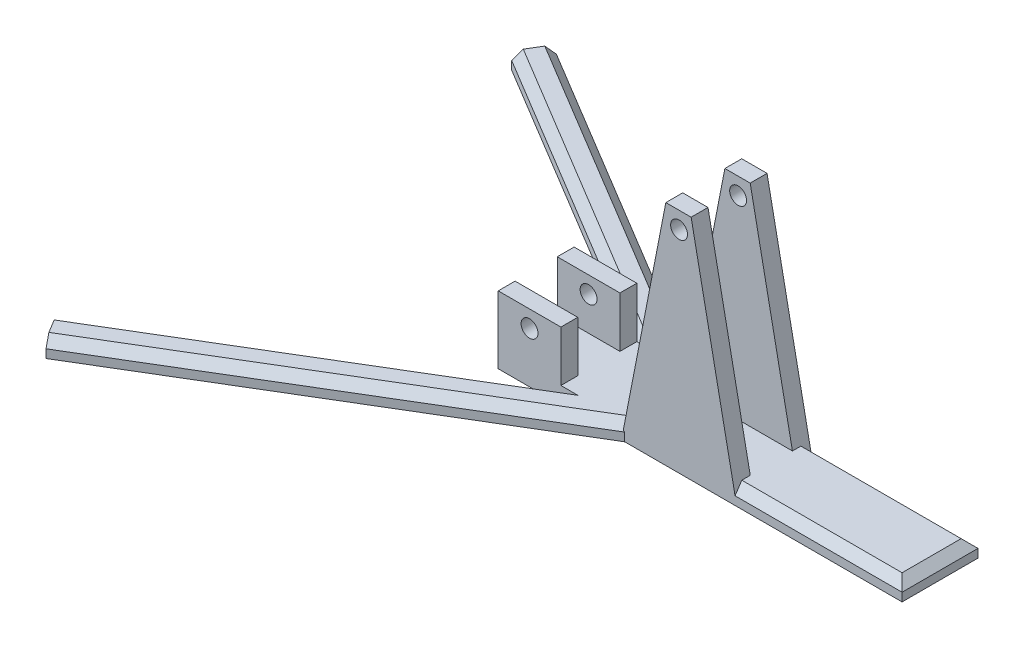
SolidWorks part; units mm, degrees
ref_plane "Plan de face" through (0, 0, 0) normal (0, 0, 1) x (1, 0, 0)
ref_plane "Plan de dessus" through (0, 0, 0) normal (0, 1, 0) x (1, 0, 0)
ref_plane "Plan de droite" through (0, 0, 0) normal (1, 0, 0) x (0, 0, -1)
sketch "Esquisse1" plane through (0, 0, 0) normal (0, 0, 1) x (1, 0, 0)
  line L0 (470.8452, 150) -> (470.8452, 60.3293) construction
  line L1 (455.1625, 170) -> (485.1625, 170)
  line L2 (485.1625, 170) -> (535.2448, -80)
  line L3 (455.1625, 170) -> (406.4457, -80)
  line L4 (406.4457, -80) -> (535.2448, -80)
  line L5 (470.8452, 150) -> (470.8452, -310) construction
  circle A1 centre (470.8452, 150) radius 10
  point P0 (470.8452, -80)
  dimension "D1" = 30
  dimension "D2" = 20
  dimension "D3" = 250
  dimension "D4" = 128.799
extrude "Boss.-Extru.1" add sketch "Esquisse1" along normal blind 20
sketch "Esquisse2" plane through (0, -80, 0) normal (0, -1, 0) x (1, 0, 0)
  line L0 (-234.755, -67.7186) -> (264.6606, -67.7186) construction
  line L1 (735.2448, 20) -> (406.4457, 20)
  line L2 (735.2448, 20) -> (735.2448, -70)
  line L3 (735.2448, -25) -> (406.4457, -25)
  line L4 (406.4457, 20) -> (406.4457, -70)
  line L5 (406.4457, -25) -> (-42.0042, 244.4559)
  line L6 (406.4457, 20) -> (-22.1379, 277.519)
  line L7 (-42.0042, 244.4559) -> (-22.1379, 277.519)
  line L8 (406.4457, -25) -> (136.0288, -25) construction
  line L9 (-42.0042, -294.4559) -> (-22.1379, -327.519)
  line L10 (406.4457, -70) -> (-22.1379, -327.519)
  line L11 (406.4457, -25) -> (-42.0042, -294.4559)
  line L12 (735.2448, -70) -> (406.4457, -70)
  line L13 (406.4457, 0) -> (535.2448, 0) construction
  line L14 (535.2448, 20) -> (535.2448, 0) construction
  line L15 (406.4457, 0) -> (535.2448, 0)
  line L16 (535.2448, 20) -> (535.2448, 0)
  line L17 (406.4457, -50) -> (535.2448, -50)
  line L18 (535.2448, -50) -> (535.2448, -70)
  line L20 (406.4457, 20) -> (256.4457, 20)
  line L21 (406.4457, 20) -> (406.4457, -70)
  line L22 (406.4457, -70) -> (256.4457, -70)
  line L23 (256.4457, 20) -> (256.4457, -70)
  line L24 (256.4457, -70) -> (330.7488, -70)
  line L25 (256.4457, -70) -> (256.4457, -50)
  line L26 (256.4457, -50) -> (330.7488, -50)
  line L27 (330.7488, -70) -> (330.7488, -50)
  line L28 (256.4457, 20) -> (330.7488, 20)
  line L29 (256.4457, 20) -> (256.4457, 0)
  line L30 (256.4457, 0) -> (330.7488, 0)
  line L31 (330.7488, 20) -> (330.7488, 0)
  point P5 (735.2448, -25)
  point P28 (535.2448, -50)
  point P29 (406.4457, -50)
  line M7 (406.4457, 0) -> (535.2448, 0)
  line M8 (535.2448, 0) -> (535.2448, 20)
  line M9 (535.2448, 20) -> (406.4457, 20)
  line M10 (406.4457, 20) -> (406.4457, 0)
  dimension "D1" = 200
  dimension "D2" = 31
  dimension "D3" = 90
  dimension "D4" = 500
  dimension "D5" = 150
  dimension "90" = 90
extrude "Boss.-Extru.2" add sketch "Esquisse2" along normal blind 20 contours L4 L3 L2 L1 M7 M8 | M10 M7 M8 M9 | L7 L5 L4 L6 M10 | L18 L17 L4 L12 | L17 L18 L12 L2 L3 L4 | L4 L11 L9 L10 | L8 L5 L20 L31 L30 L23 | L11 L8 L23 L26 L27 L22 | L31 L20 L23 L30 | L22 L27 L26 L23 | L20 L5 L4 M10 | L22 L4 L11 region at (591.9253, -80, -5.135) region at (470.8452, -80, 10) region at (591.9253, -80, -44.865) region at (169.0059, -80, 140.6827) region at (381.4815, -80, 5) region at (323.6026, -80, -11.2217) region at (323.6026, -80, -38.7783) region at (381.4815, -80, -55) region at (470.8452, -80, -60) region at (169.0059, -80, -190.6827) region at (293.5972, -80, 10) region at (293.5972, -80, -60)
ref_plane "Plan2" through (14.9528, -24.7288, -77.7186) normal (0, 0, -1) x (-1, 0, 0)
sketch "Esquisse3" plane through (0, 0, -70) normal (0, 0, -1) x (-1, 0, 0)
  line L4 (-406.4457, -80) -> (-455.1625, 170)
  line L5 (-455.1625, 170) -> (-485.1625, 170)
  line L6 (-485.1625, 170) -> (-535.2448, -80)
  line L7 (-535.2448, -80) -> (-406.4457, -80)
  line L8 (-406.4457, -80) -> (-455.1625, 170)
  line L9 (-455.1625, 170) -> (-485.1625, 170)
  line L10 (-485.1625, 170) -> (-535.2448, -80)
  line L11 (-535.2448, -80) -> (-406.4457, -80)
  circle A0 centre (-470.8452, 150) radius 10 construction
  circle A1 centre (-470.8452, 150) radius 10
  dimension "D1" = 0
extrude "Boss.-Extru.3" add sketch "Esquisse3" against normal blind 20
chamfer "Chanfrein3" distance 10 angle 45 4 edges at (144.7745, -80, 132.228) (144.7745, -80, -182.228) (192.1539, -80, 148.7595) (192.1539, -80, -198.7595)
extrude "Boss.-Extru.4" add sketch "Esquisse2<5>" against normal blind 60 contours L22 L27 L26 L23 | L31 L20 L23 L30 region at (293.5972, -80, 10) region at (293.5972, -80, -60)
sketch "Esquisse2<5>" plane through (0, -80, 0) normal (0, -1, 0) x (1, 0, 0) same geometry as "Esquisse2"
sketch "Esquisse4" plane through (0, 0, -70) normal (0, 0, -1) x (-1, 0, 0)
  line L0 (-330.7488, -20) -> (-256.4457, -60) construction
  line L1 (-256.4457, -100) -> (-256.4457, -20) construction
  circle A0 centre (-293.5972, -40) radius 10
  dimension "D1" = 20
extrude "Enlèv. mat.-Extru.1" cut sketch "Esquisse4" against normal through all
chamfer "Chanfrein2" distance 10 angle 45 3 edges at (635.2448, -80, -70) (635.2448, -80, 20) (735.2448, -80, -25)
